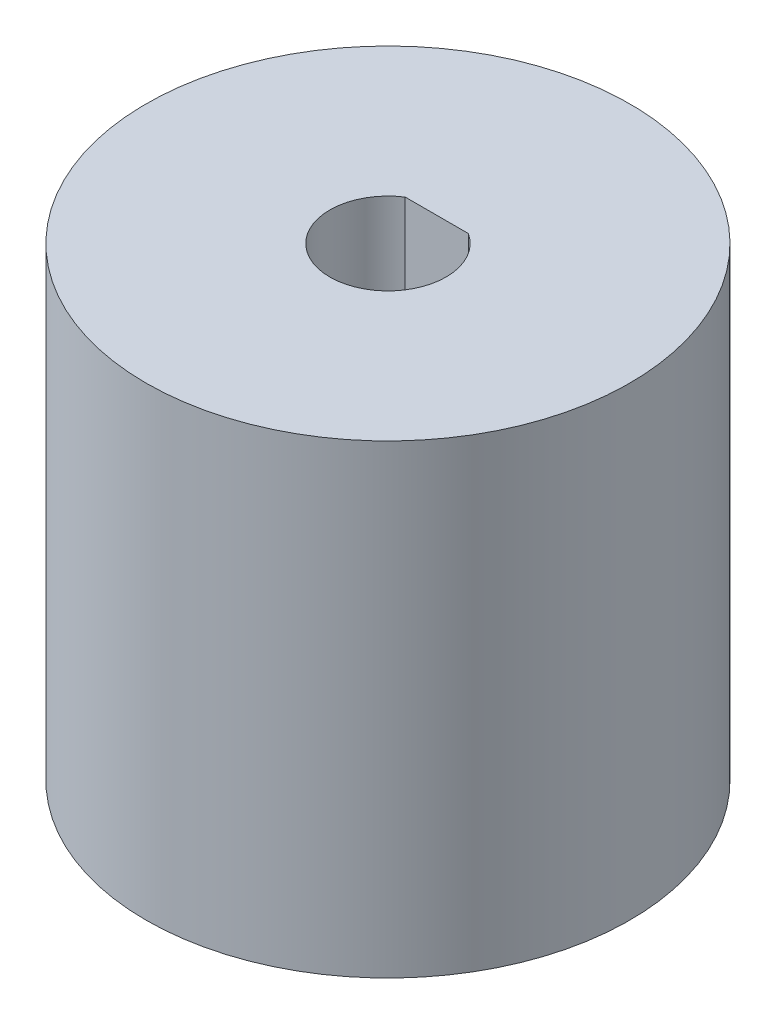
SolidWorks part; units mm, degrees
material "PBT General Purpose"
ref_plane "Front Plane" through (0, 0, 0) normal (0, 0, 1) x (1, 0, 0)
ref_plane "Top Plane" through (0, 0, 0) normal (0, 1, 0) x (1, 0, 0)
ref_plane "Right Plane" through (0, 0, 0) normal (1, 0, 0) x (0, 0, -1)
sketch "Sketch1" plane through (0, 0, 0) normal (0, 1, 0) x (1, 0, 0)
  line L0 (0, -3.175) -> (5.0633, -3.175) construction
  line L1 (0, -3.0734) -> (0, 3.0734) construction
  line L2 (0, -3.175) -> (-5.0664, -3.175) construction
  line L3 (0, 2.667) -> (-1.7227, 2.667)
  line L6 (0, 2.667) -> (1.7227, 2.667)
  circle A0 centre (0, 0) radius 13.208
  circle A1 centre (0, 0) radius 3.175
  point P8 (0, 2.667)
extrude "Boss-Extrude4" add sketch "Sketch1" along normal blind 25.4 contours A0 A1 | L6 A1 L3 | L3 A1 L6 region at (0, 0, 0.1118) region at (0, 0, -2.8717) region at (-12.8344, 0, 0)
extrude "Cut-Extrude3" cut sketch "Sketch1<6>" along normal through all contours L3 A1 L6 region at (0, 0, 0.1118)
sketch "Sketch1<6>" plane through (0, 0, 0) normal (0, 1, 0) x (1, 0, 0) same geometry as "Sketch1"
extrude "Cut-Extrude4" cut sketch "Sketch1<7>" along normal blind 5.588 contours L6 A1 L3 region at (0, 0, -2.8717)
sketch "Sketch1<7>" plane through (0, 0, 0) normal (0, 1, 0) x (1, 0, 0) same geometry as "Sketch1"
